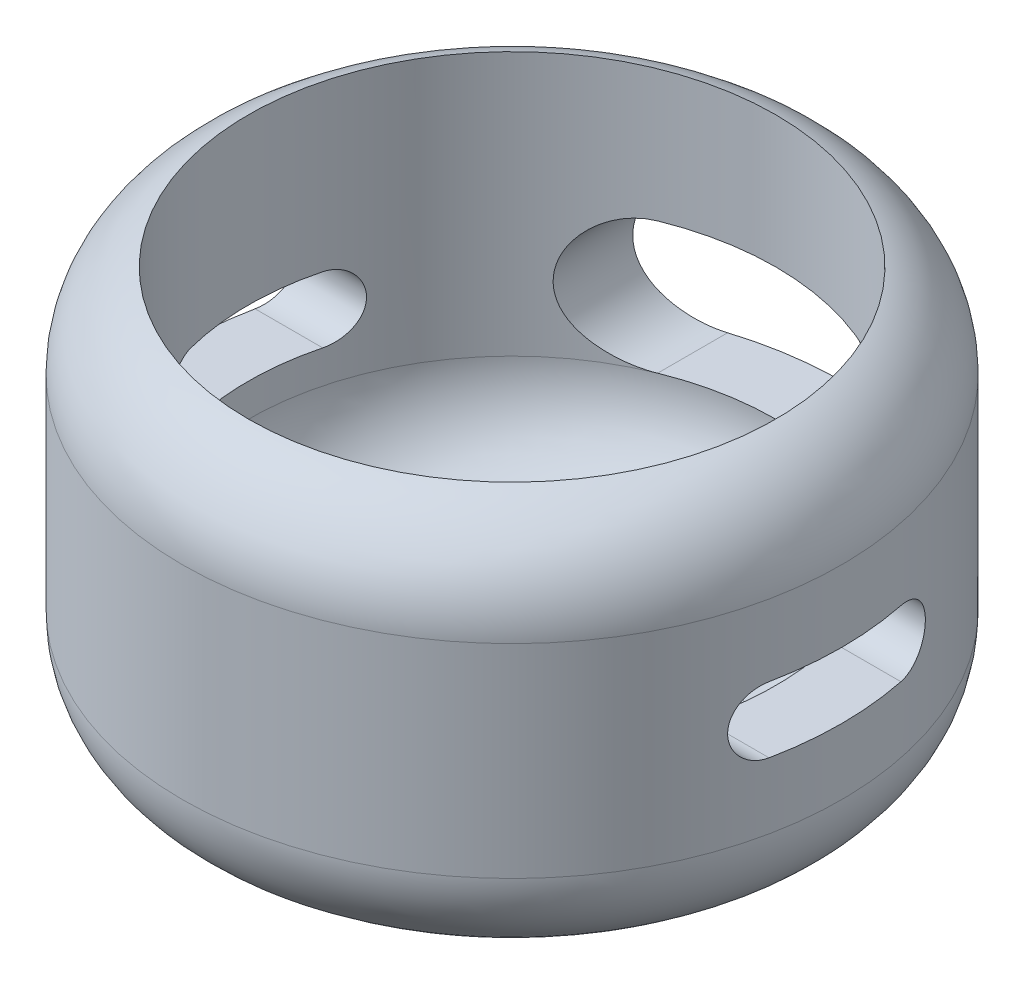
SolidWorks part; units mm, degrees
ref_plane "前视基准面" through (0, 0, 0) normal (0, 0, 1) x (1, 0, 0)
ref_plane "上视基准面" through (0, 0, 0) normal (0, 1, 0) x (1, 0, 0)
ref_plane "右视基准面" through (0, 0, 0) normal (1, 0, 0) x (0, 0, -1)
sketch "草图1" plane through (0, 0, 0) normal (0, 1, 0) x (1, 0, 0)
  circle A0 centre (3.8777, 2.7704) radius 7.5 construction
  circle A1 centre (3.8777, 2.7704) radius 10
  dimension "D1" = 15
  dimension "D2" = 20
extrude "凸台-拉伸1" add sketch "草图1" along normal blind 12
sketch "草图2" plane through (0, 0, 0) normal (0, 0, 1) x (1, 0, 0)
  line L0 (0.8777, 6) -> (6.8777, 6) construction
  line L1 (0.8777, 8) -> (6.8777, 8)
  line L2 (0.8777, 4) -> (6.8777, 4)
  line L3 (13.8777, 12) -> (-6.1223, 12) construction
  line L5 (-6.1223, 12) -> (-6.1223, 0) construction
  arc A0 (0.8777, 8) -> (0.8777, 4) centre (0.8777, 6) ccw
  arc A1 (6.8777, 4) -> (6.8777, 8) centre (6.8777, 6) ccw
  point P2 (3.8777, 6)
  dimension "D4" = 2
  dimension "D1" = 6
  dimension "D2" = 10
  dimension "D3" = 6
extrude "切除-拉伸1" cut sketch "草图2" against normal through all
sketch "草图3" plane through (0, 12, 0) normal (0, 1, 0) x (1, 0, 0)
  circle A1 centre (3.8777, 2.7704) radius 8
  dimension "D1" = 16
extrude "切除-拉伸2" cut sketch "草图3" against normal blind 11
fillet "圆角1" radius 3 3 edges at (3.8777, 12, 7.2296) (3.8777, 1, 5.2296) (3.8777, 0, 7.2296)
sketch "草图4" plane through (0, 0, 0) normal (1, 0, 0) x (0, 0, -1)
  line L0 (0.7704, 6) -> (4.7704, 6) construction
  line L1 (0.7704, 7) -> (4.7704, 7)
  line L2 (0.7704, 5) -> (4.7704, 5)
  line L4 (-7.2296, 9.1716) -> (-7.2296, 3) construction
  line L5 (-5.2296, 12) -> (10.7704, 12) construction
  arc A0 (0.7704, 7) -> (0.7704, 5) centre (0.7704, 6) ccw
  arc A1 (4.7704, 5) -> (4.7704, 7) centre (4.7704, 6) ccw
  point P2 (2.7704, 6)
  dimension "D2" = 1
  dimension "D1" = 10
  dimension "D3" = 4
  dimension "D4" = 6
extrude "切除-拉伸3" cut sketch "草图4" against normal through all and the other way through all
